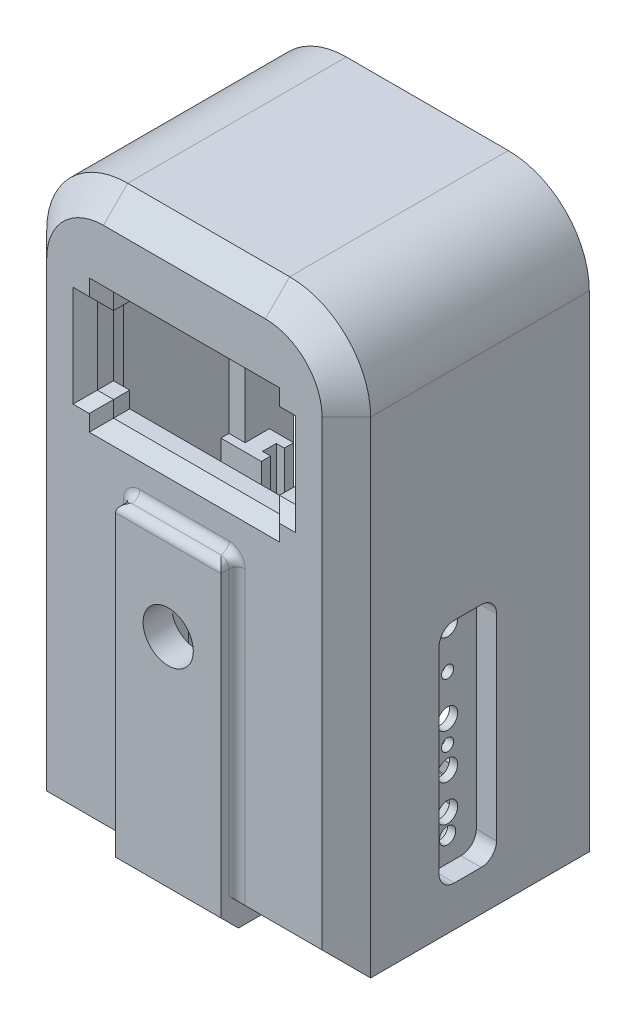
SolidWorks part; units mm, degrees
ref_plane "Alzado" through (0, 0, 0) normal (0, 0, 1) x (1, 0, 0)
ref_plane "Planta" through (0, 0, 0) normal (0, 1, 0) x (1, 0, 0)
ref_plane "Vista lateral" through (0, 0, 0) normal (1, 0, 0) x (0, 0, -1)
sketch "Croquis1" plane through (0, 0, 0) normal (0, 0, 1) x (1, 0, 0)
  line L1 (-43.0607, 30.3006) -> (-3.0607, 30.3006)
  line L2 (-43.0607, 30.3006) -> (-43.0607, -39.6994)
  line L3 (-43.0607, -39.6994) -> (-3.0607, -39.6994)
  line L4 (-3.0607, 30.3006) -> (-3.0607, -39.6994)
  dimension "D1" = 70
  dimension "D2" = 40
extrude "Saliente-Extruir1" add sketch "Croquis1" against normal blind 30
fillet "Redondeo1" radius 10 2 edges at (-43.0607, 30.3006, -15) (-3.0607, 30.3006, -15)
sketch "Croquis3" plane through (-3.0607, 0, 0) normal (1, 0, 0) x (0, 0, -1)
  line L0 (30, -39.6994) -> (0, -39.6994) construction
  line L1 (13.35, -6.5994) -> (16.65, -6.5994)
  line L2 (11.45, -8.4994) -> (11.45, -32.7994)
  line L3 (13.35, -34.6994) -> (16.65, -34.6994)
  line L4 (18.55, -8.4994) -> (18.55, -32.7994)
  arc A0 (11.45, -32.7994) -> (13.35, -34.6994) centre (13.35, -32.7994) ccw
  arc A1 (16.65, -34.6994) -> (18.55, -32.7994) centre (16.65, -32.7994) ccw
  arc A2 (16.65, -6.5994) -> (18.55, -8.4994) centre (16.65, -8.4994) cw
  arc A3 (13.35, -6.5994) -> (11.45, -8.4994) centre (13.35, -8.4994) ccw
  point P6 (15, -39.6994)
  point P7 (15, -34.6994)
  point P12 (11.45, -34.6994)
  point P17 (18.55, -6.5994)
  point P20 (11.45, -6.5994)
  dimension "D4" = 1.9
  dimension "D1" = 5
  dimension "D2" = 28.1
  dimension "D3" = 7.1
fillet "Redondeo3" radius 3 6 edges at (-43.0607, -9.6994, 0) (-40.1317, 27.3717, 0) (-23.0607, 30.3006, 0) (-3.0607, -9.6994, 0) (-5.9896, 27.3717, 0) (-23.0607, -39.6994, 0) profile chamfer
sketch "Croquis16" plane through (-43.0607, 0, 0) normal (-1, 0, 0) x (0, 0, 1)
  line L1 (-27.5, 15.3006) -> (-5.5, 15.3006)
  line L2 (-27.5, 15.3006) -> (-27.5, -39.6994)
  line L3 (-27.5, -39.6994) -> (-5.5, -39.6994)
  line L4 (-5.5, 15.3006) -> (-5.5, -39.6994)
  line L6 (-30, -39.6994) -> (-3, -39.6994) construction
  point P8 (-16.5, -39.6994)
  point P9 (-16.5, -39.6994)
  dimension "D1" = 22
  dimension "D2" = 55
extrude "Saliente-Extruir5" add sketch "Croquis16" along normal blind 2
ref_plane "Plano1" through (-23.0607, 0, 0) normal (-1, 0, 0) x (0, 0, 1)
sketch "Croquis17" plane through (-23.0607, 0, 0) normal (-1, 0, 0) x (0, 0, 1)
  line L0 (0, 0.3006) -> (2, 0.3006)
  line L1 (0, 20.3006) -> (0, -36.6994) construction
  line L2 (2, 0.3006) -> (2, -37.5278)
  line L3 (2, -37.5278) -> (-0.1716, -39.6994)
  line L4 (-0.1716, -39.6994) -> (-3, -39.6994)
  line L5 (-3, -39.6994) -> (0, -36.6994)
  line L6 (0, -36.6994) -> (0, 0.3006)
  dimension "D1" = 2
  dimension "D2" = 2
  dimension "D3" = 40
extrude "Saliente-Extruir6" add sketch "Croquis17" along normal mid plane 13
shell "Vaciado1" thickness 3.5 removed face at (-23.0607, 4.3243, -30)
chamfer "Chaflán4" distance 2 angle 45 1 edges at (-45.0607, -39.6994, -16.5)
fillet "Redondeo5" radius 1 6 edges at (-43.0607, -12.1994, -5.5) (-43.0607, -12.1994, -27.5) (-44.0607, 15.3006, -5.5) (-45.0607, 15.3006, -16.5) (-44.0607, 15.3006, -27.5) (-43.0607, 15.3006, -16.5)
fillet "Redondeo4" radius 1 6 edges at (-29.5607, -18.1994, 0) (-16.5607, -18.1994, 0) (-23.0607, 0.3006, 2) (-29.5607, 0.3006, 1) (-23.0607, 0.3006, 0) (-16.5607, 0.3006, 1)
extrude "Cortar-Extruir2" cut sketch "Croquis3" against normal offset from surface (2.5 mm away) 1 contours L1 A2 L4 A1 L3 A0 L2 A3 up to face at (-6.5607, -7.9494, -17.2249)
sketch "Croquis2" plane through (0, 0, 0) normal (0, 0, 1) x (1, 0, 0)
  line L0 (-3.0607, 30.3006) -> (-43.0607, 30.3006) construction
  line L1 (-35.3107, 19.3006) -> (-10.8107, 19.3006)
  line L2 (-35.3107, 19.3006) -> (-35.3107, 5.8006)
  line L3 (-35.3107, 5.8006) -> (-10.8107, 5.8006)
  line L4 (-10.8107, 19.3006) -> (-10.8107, 5.8006)
  line L12 (-40.0607, -39.6994) -> (-6.0607, -39.6994) construction
  point P12 (-23.0607, -39.6994)
  point P13 (-23.0607, 5.8006)
  dimension "D1" = 24.5
  dimension "D2" = 13.5
  dimension "D5" = 11
extrude "Cortar-Extruir1" cut sketch "Croquis2" against normal up to next
sketch "Croquis11" plane through (-5.5607, 0, 0) normal (1, 0, 0) x (0, 0, -1)
  line L0 (13.35, -34.6994) -> (16.65, -34.6994) construction
  line L1 (13.35, -34.6994) -> (16.65, -34.6994) construction
  circle A0 centre (15, -31.6994) radius 1
  circle A1 centre (15, -29.1994) radius 1.25
  circle A2 centre (15, -24.6994) radius 1.25
  circle A3 centre (15, -9.1994) radius 1.25
  circle A4 centre (15, -19.1994) radius 1.25
  circle A5 centre (15, -14.1994) radius 0.75
  circle A6 centre (15, -21.9994) radius 0.75
  point P10 (15, -34.6994)
  dimension "D1" = 2
  dimension "D2" = 2.5
  dimension "D3" = 2.5
  dimension "D5" = 2.5
  dimension "D6" = 4.5
  dimension "D7" = 20
  dimension "D8" = 2.5
  dimension "D9" = 5.5
  dimension "D10" = 1.5
  dimension "D4" = 3
  dimension "D11" = 5
  dimension "D12" = 2.7
extrude "Cortar-Extruir3" cut sketch "Croquis11" against normal up to next
sketch "Croquis12" plane through (0, 0, -3.5) normal (0, 0, -1) x (-1, 0, 0)
  line L1 (14.0618, 21.5506) -> (13.3112, 22.8506)
  line L2 (13.3112, 22.8506) -> (11.8101, 22.8506)
  line L3 (11.8101, 22.8506) -> (11.0595, 21.5506)
  line L4 (11.0595, 21.5506) -> (11.8101, 20.2506)
  line L5 (11.8101, 20.2506) -> (13.3112, 20.2506)
  line L6 (13.3112, 20.2506) -> (14.0618, 21.5506)
  line L7 (35.0618, 21.5506) -> (34.3112, 22.8506)
  line L8 (34.3112, 22.8506) -> (32.8101, 22.8506)
  line L9 (32.8101, 22.8506) -> (32.0595, 21.5506)
  line L10 (32.0595, 21.5506) -> (32.8101, 20.2506)
  line L11 (32.8101, 20.2506) -> (34.3112, 20.2506)
  line L12 (34.3112, 20.2506) -> (35.0618, 21.5506)
  line L13 (14.0618, -0.4494) -> (13.3112, 0.8506)
  line L14 (13.3112, 0.8506) -> (11.8101, 0.8506)
  line L15 (11.8101, 0.8506) -> (11.0595, -0.4494)
  line L16 (11.0595, -0.4494) -> (11.8101, -1.7494)
  line L17 (11.8101, -1.7494) -> (13.3112, -1.7494)
  line L18 (13.3112, -1.7494) -> (14.0618, -0.4494)
  line L19 (35.0618, -0.4494) -> (34.3112, 0.8506)
  line L20 (34.3112, 0.8506) -> (32.8101, 0.8506)
  line L21 (32.8101, 0.8506) -> (32.0595, -0.4494)
  line L22 (32.0595, -0.4494) -> (32.8101, -1.7494)
  line L23 (32.8101, -1.7494) -> (34.3112, -1.7494)
  line L24 (34.3112, -1.7494) -> (35.0618, -0.4494)
  line L26 (23.0607, 5.8006) -> (23.0607, 25.8509) construction
  line L27 (10.8107, 5.8006) -> (35.3107, 5.8006) construction
  line L28 (13.0607, 25.8509) -> (33.0607, 25.8509) construction
  line L29 (35.3107, 19.3006) -> (10.8107, 19.3006) construction
  circle A0 centre (12.5607, 21.5506) radius 1.3 construction
  circle A1 centre (33.5607, 21.5506) radius 1.3 construction
  circle A2 centre (12.5607, -0.4494) radius 1.3 construction
  circle A3 centre (33.5607, -0.4494) radius 1.3 construction
  dimension "D1" = 2.6
  dimension "D2" = 2.25
  dimension "D4" = 22
  dimension "D5" = 21
extrude "Cortar-Extruir4" cut sketch "Croquis12" against normal blind 1.4
sketch "Croquis13" plane through (0, 0, 0) normal (0, 0, 1) x (1, 0, 0)
  line L1 (-35.3107, 19.3006) -> (-33.3107, 19.3006)
  line L2 (-35.3107, 19.3006) -> (-35.3107, 17.3006)
  line L3 (-35.3107, 17.3006) -> (-33.3107, 17.3006)
  line L4 (-33.3107, 19.3006) -> (-33.3107, 17.3006)
  line L5 (-35.3107, 5.8006) -> (-33.3107, 5.8006)
  line L6 (-35.3107, 5.8006) -> (-35.3107, 7.8006)
  line L7 (-35.3107, 7.8006) -> (-33.3107, 7.8006)
  line L8 (-33.3107, 5.8006) -> (-33.3107, 7.8006)
  line L9 (-10.8107, 5.8006) -> (-12.8107, 5.8006)
  line L10 (-10.8107, 5.8006) -> (-10.8107, 7.8006)
  line L11 (-10.8107, 7.8006) -> (-12.8107, 7.8006)
  line L12 (-12.8107, 5.8006) -> (-12.8107, 7.8006)
  line L13 (-10.8107, 19.3006) -> (-12.8107, 19.3006)
  line L14 (-10.8107, 19.3006) -> (-10.8107, 17.3006)
  line L15 (-10.8107, 17.3006) -> (-12.8107, 17.3006)
  line L16 (-12.8107, 19.3006) -> (-12.8107, 17.3006)
  dimension "D1" = 2
extrude "Saliente-Extruir2" add sketch "Croquis13" against normal up to surface (3.5 mm away) up to face at (-33.5607, 21.5506, -3.5)
chamfer "Chaflán1" distance 1.5 angle 45 12 edges at (-12.8107, 18.3006, 0) (-11.8107, 17.3006, 0) (-10.8107, 12.5506, 0) (-11.8107, 7.8006, 0) (-12.8107, 6.8006, 0) (-23.0607, 5.8006, 0) (-33.3107, 6.8006, 0) (-34.3107, 7.8006, 0) (-35.3107, 12.5506, 0) (-34.3107, 17.3006, 0) (-33.3107, 18.3006, 0) (-23.0607, 19.3006, 0)
sketch "Croquis18" plane through (0, 0, 0) normal (0, 0, 1) x (1, 0, 0)
  line L0 (-3.0607, -39.6994) -> (-16.5607, -39.6994) construction
  line L1 (-29.5607, -37.5278) -> (-16.5607, -37.5278) construction
  circle A0 centre (-23.0607, -10.6994) radius 3.1
  point P8 (-23.0607, -37.5278)
  dimension "D1" = 6.2
  dimension "D2" = 29
extrude "Cortar-Extruir5" cut sketch "Croquis18" against normal through all both and the other way through all
sketch "Croquis20" plane through (0, -36.1994, 0) normal (0, 1, 0) x (1, 0, 0)
  line L0 (-39.5607, 30) -> (-6.5607, 30) construction
  line L1 (-38.5607, 27) -> (-7.5607, 27)
  line L7 (-38.5607, 23) -> (-7.5607, 23)
  line L9 (-38.5607, 27) -> (-38.5607, 23)
  line L10 (-7.5607, 27) -> (-7.5607, 23)
  line L11 (-37.5607, 25.85) -> (-37.5607, 24.15)
  line L12 (-37.5607, 25.85) -> (-8.5607, 25.85)
  line L13 (-38.5607, 25.85) -> (-38.5607, 24.15)
  line L14 (-37.5607, 24.15) -> (-8.5607, 24.15)
  line L15 (-7.5607, 25.85) -> (-7.5607, 24.15)
  line L16 (-8.5607, 25.85) -> (-8.5607, 24.15)
  point P10 (-23.0607, 30)
  point P11 (-23.0607, 27)
  point P16 (-8.5607, 25)
  point P17 (-7.5607, 25)
  point P18 (-23.0607, 25.85)
  dimension "D1" = 4
  dimension "D2" = 3
  dimension "D3" = 1.7
  dimension "D4" = 31
  dimension "D5" = 29
extrude "Saliente-Extruir7" add sketch "Croquis20" along normal blind 25 contours L10 L1 L9 L7 L12 L16 L14 L11 region at (-23.0607, -36.1994, -26.6874)
sketch "Croquis22" plane through (0, 0, -27) normal (0, 0, -1) x (-1, 0, 0)
  line L0 (38.5607, -11.1994) -> (7.5607, -11.1994) construction
  line L1 (9.5607, -11.1994) -> (36.5607, -11.1994)
  line L2 (9.5607, -11.1994) -> (9.5607, -34.6994)
  line L3 (9.5607, -34.6994) -> (36.5607, -34.6994)
  line L4 (36.5607, -11.1994) -> (36.5607, -34.6994)
  line L5 (7.5607, -11.1994) -> (7.5607, -36.1994) construction
  line L6 (38.5607, -11.1994) -> (38.5607, -36.1994) construction
  line L7 (38.5607, -36.1994) -> (7.5607, -36.1994) construction
  dimension "D1" = 2
  dimension "D2" = 2
  dimension "D3" = 1.5
extrude "Cortar-Extruir6" cut sketch "Croquis22" against normal blind 4
sketch "Croquis24" plane through (0, 0, -30) normal (0, 0, -1) x (-1, 0, 0)
  line L0 (13.0607, 30.3006) -> (33.0607, 30.3006) construction
  line L1 (19.0618, 28.5506) -> (18.3112, 29.8506)
  line L2 (18.3112, 29.8506) -> (16.8101, 29.8506)
  line L3 (16.8101, 29.8506) -> (16.0595, 28.5506)
  line L4 (16.0595, 28.5506) -> (16.8101, 27.2506)
  line L5 (16.8101, 27.2506) -> (18.3112, 27.2506)
  line L6 (18.3112, 27.2506) -> (19.0618, 28.5506)
  line L8 (30.0618, 28.5506) -> (29.3112, 29.8506)
  line L9 (29.3112, 29.8506) -> (27.8101, 29.8506)
  line L10 (27.8101, 29.8506) -> (27.0595, 28.5506)
  line L11 (27.0595, 28.5506) -> (27.8101, 27.2506)
  line L12 (27.8101, 27.2506) -> (29.3112, 27.2506)
  line L13 (29.3112, 27.2506) -> (30.0618, 28.5506)
  line L14 (6.4618, -37.9494) -> (5.7112, -36.6494)
  line L15 (5.7112, -36.6494) -> (4.2101, -36.6494)
  line L16 (4.2101, -36.6494) -> (3.4595, -37.9494)
  line L17 (3.4595, -37.9494) -> (4.2101, -39.2494)
  line L18 (4.2101, -39.2494) -> (5.7112, -39.2494)
  line L19 (5.7112, -39.2494) -> (6.4618, -37.9494)
  line L20 (24.5618, -37.9494) -> (23.8112, -36.6494)
  line L21 (23.8112, -36.6494) -> (22.3101, -36.6494)
  line L22 (22.3101, -36.6494) -> (21.5595, -37.9494)
  line L23 (21.5595, -37.9494) -> (22.3101, -39.2494)
  line L24 (22.3101, -39.2494) -> (23.8112, -39.2494)
  line L25 (23.8112, -39.2494) -> (24.5618, -37.9494)
  line L26 (42.6618, -37.9494) -> (41.9112, -36.6494)
  line L27 (41.9112, -36.6494) -> (40.4101, -36.6494)
  line L28 (40.4101, -36.6494) -> (39.6595, -37.9494)
  line L29 (39.6595, -37.9494) -> (40.4101, -39.2494)
  line L30 (40.4101, -39.2494) -> (41.9112, -39.2494)
  line L31 (41.9112, -39.2494) -> (42.6618, -37.9494)
  line L32 (42.6107, -18.7) -> (42.6107, -17.1988)
  line L33 (42.6107, -17.1988) -> (41.3107, -16.4483)
  line L34 (41.3107, -16.4483) -> (40.0107, -17.1988)
  line L35 (40.0107, -17.1988) -> (40.0107, -18.7)
  line L36 (40.0107, -18.7) -> (41.3107, -19.4505)
  line L37 (41.3107, -19.4505) -> (42.6107, -18.7)
  line L38 (42.6107, 16.3) -> (42.6107, 17.8012)
  line L39 (42.6107, 17.8012) -> (41.3107, 18.5517)
  line L40 (41.3107, 18.5517) -> (40.0107, 17.8012)
  line L41 (40.0107, 17.8012) -> (40.0107, 16.3)
  line L42 (40.0107, 16.3) -> (41.3107, 15.5495)
  line L43 (41.3107, 15.5495) -> (42.6107, 16.3)
  line L44 (6.1107, -18.7) -> (6.1107, -17.1988)
  line L45 (6.1107, -17.1988) -> (4.8107, -16.4483)
  line L46 (4.8107, -16.4483) -> (3.5107, -17.1988)
  line L47 (3.5107, -17.1988) -> (3.5107, -18.7)
  line L48 (3.5107, -18.7) -> (4.8107, -19.4505)
  line L49 (4.8107, -19.4505) -> (6.1107, -18.7)
  line L50 (6.1107, 16.3) -> (6.1107, 17.8012)
  line L51 (6.1107, 17.8012) -> (4.8107, 18.5517)
  line L52 (4.8107, 18.5517) -> (3.5107, 17.8012)
  line L53 (3.5107, 17.8012) -> (3.5107, 16.3)
  line L54 (3.5107, 16.3) -> (4.8107, 15.5495)
  line L55 (4.8107, 15.5495) -> (6.1107, 16.3)
  line L56 (43.0607, 20.3006) -> (43.0607, -39.6994) construction
  line L58 (43.0607, -39.6994) -> (3.0607, -39.6994) construction
  line L59 (3.0607, -39.6994) -> (3.0607, 20.3006) construction
  circle A0 centre (17.5607, 28.5506) radius 1.3 construction
  circle A1 centre (28.5607, 28.5506) radius 1.3 construction
  circle A2 centre (4.9607, -37.9494) radius 1.3 construction
  circle A3 centre (23.0607, -37.9494) radius 1.3 construction
  circle A4 centre (41.1607, -37.9494) radius 1.3 construction
  circle A5 centre (41.3107, -17.9494) radius 1.3 construction
  circle A6 centre (41.3107, 17.0506) radius 1.3 construction
  circle A7 centre (4.8107, -17.9494) radius 1.3 construction
  circle A8 centre (4.8107, 17.0506) radius 1.3 construction
  point P81 (23.0607, -39.6994)
  dimension "D1" = 2.6
  dimension "D10" = 1.9
  dimension "D2" = 1.75
  dimension "D4" = 1.75
  dimension "D6" = 1.75
  dimension "D7" = 1.9
  dimension "D12" = 1.75
  dimension "D13" = 20
  dimension "D14" = 35
  dimension "D15" = 14.5
  dimension "D16" = 14.5
extrude "Cortar-Extruir7" cut sketch "Croquis24" against normal blind 2
sketch "Croquis27" plane through (-38.5607, 0, 0) normal (-1, 0, 0) x (0, 0, 1)
  line L1 (-27, -11.1994) -> (-23, -11.1994)
  line L2 (-27, -11.1994) -> (-27, -36.1994)
  line L3 (-27, -36.1994) -> (-23, -36.1994)
  line L4 (-23, -11.1994) -> (-23, -36.1994)
extrude "Saliente-Extruir8" add sketch "Croquis27" along normal up to next
sketch "Croquis28" plane through (-7.5607, 0, 0) normal (1, 0, 0) x (0, 0, -1)
  line L1 (23, -11.1994) -> (27, -11.1994)
  line L2 (23, -11.1994) -> (23, -36.1994)
  line L3 (23, -36.1994) -> (27, -36.1994)
  line L4 (27, -11.1994) -> (27, -36.1994)
extrude "Saliente-Extruir9" add sketch "Croquis28" along normal up to next
sketch "Croquis29" plane through (0, 0, -2.1) normal (0, 0, -1) x (-1, 0, 0)
  line L4 (34.3112, 22.8506) -> (32.8101, 22.8506) construction
  line L5 (32.8101, 22.8506) -> (32.0595, 21.5506) construction
  line L7 (11.8101, 22.8506) -> (11.0595, 21.5506) construction
  line L11 (13.3112, 0.8506) -> (11.8101, 0.8506) construction
  circle A0 centre (33.5607, 21.5506) radius 0.75
  circle A1 centre (12.5607, 21.5506) radius 0.75
  circle A2 centre (12.5607, -0.4494) radius 0.75
  circle A3 centre (33.5607, -0.4494) radius 0.75
  dimension "D1" = 1.5
  dimension "D2" = 1.3
  dimension "D3" = 1.3
  dimension "D4" = 1.3
  dimension "D5" = 1.3
extrude "Cortar-Extruir8" cut sketch "Croquis29" against normal offset from surface (1.6 mm away) 0.5 up to face at (-23.0607, 12.5506, 0)
sketch "Croquis30" plane through (0, 0, -28) normal (0, 0, -1) x (-1, 0, 0)
  line L2 (29.3112, 29.8506) -> (27.8101, 29.8506) construction
  line L3 (18.3112, 29.8506) -> (16.8101, 29.8506) construction
  line L4 (42.6107, 16.3) -> (42.6107, 17.8012) construction
  line L5 (42.6107, -18.7) -> (42.6107, -17.1988) construction
  line L6 (41.9112, -36.6494) -> (40.4101, -36.6494) construction
  line L7 (23.8112, -36.6494) -> (22.3101, -36.6494) construction
  line L8 (5.7112, -36.6494) -> (4.2101, -36.6494) construction
  line L9 (3.5107, -17.1988) -> (3.5107, -18.7) construction
  line L10 (3.5107, 17.8012) -> (3.5107, 16.3) construction
  circle A0 centre (17.5607, 28.5506) radius 0.75
  circle A1 centre (28.5607, 28.5506) radius 0.75
  circle A2 centre (4.8107, 17.0506) radius 0.75
  circle A3 centre (41.3107, 17.0506) radius 0.75
  circle A4 centre (41.3107, -17.9494) radius 0.75
  circle A5 centre (41.1607, -37.9494) radius 0.75
  circle A6 centre (23.0607, -37.9494) radius 0.75
  circle A7 centre (4.9607, -37.9494) radius 0.75
  circle A8 centre (4.8107, -17.9494) radius 0.75
  point P4 (17.5607, 29.8506)
  point P24 (28.5607, 29.8506)
  point P32 (42.6107, 17.0506)
  point P35 (42.6107, -17.9494)
  point P40 (41.1607, -36.6494)
  point P47 (23.0607, -36.6494)
  point P51 (4.9607, -36.6494)
  point P56 (3.5107, -17.9494)
  point P61 (3.5107, 17.0506)
  dimension "D1" = 1.5
extrude "Cortar-Extruir9" cut sketch "Croquis30" against normal blind 3
